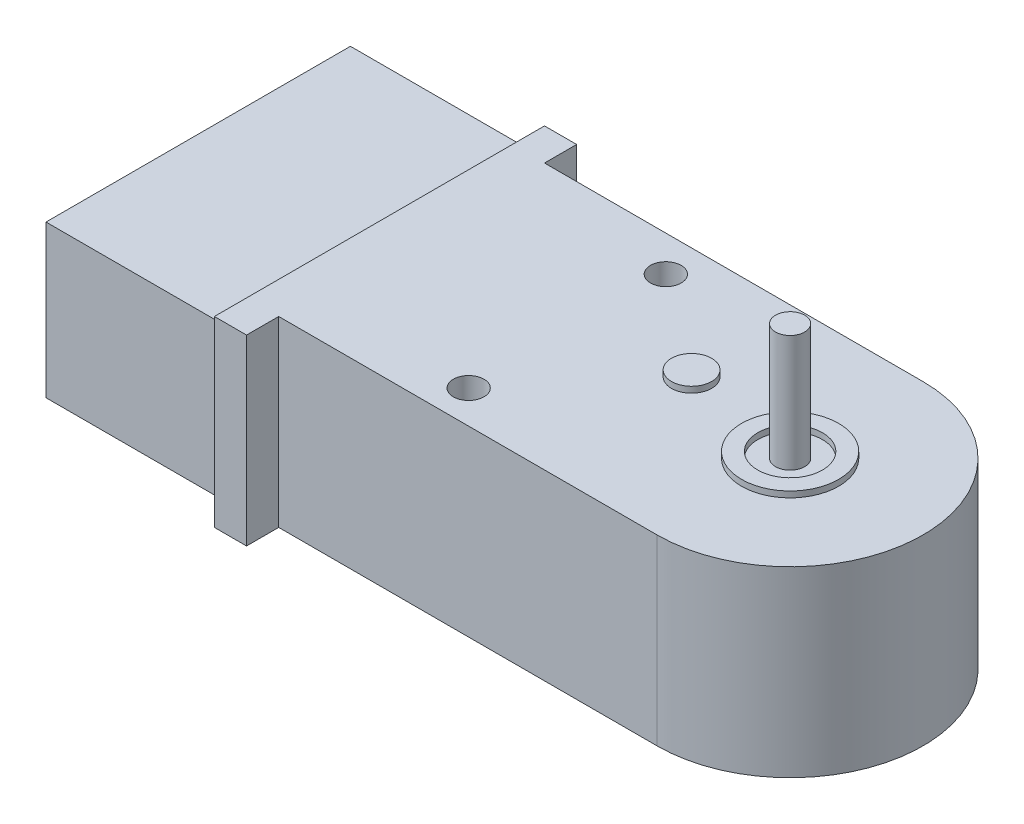
SolidWorks part; units mm, degrees
ref_plane "Front Plane" through (0, 0, 0) normal (0, 0, 1) x (1, 0, 0)
ref_plane "Top Plane" through (0, 0, 0) normal (0, 1, 0) x (1, 0, 0)
ref_plane "Right Plane" through (0, 0, 0) normal (1, 0, 0) x (0, 0, -1)
sketch "Sketch1" plane through (0, 0, 0) normal (0, 1, 0) x (1, 0, 0)
  line L0 (-30.84, 0) -> (0, 0) construction
  line L1 (0, 9.98) -> (-28.425, 9.98)
  line L2 (-28.425, 9.98) -> (-28.425, 12.395)
  line L3 (-28.425, 12.395) -> (-30.84, 12.395)
  line L4 (-30.84, 12.395) -> (-30.84, -12.395)
  line L5 (-30.84, -12.395) -> (-28.425, -12.395)
  line L6 (-28.425, -12.395) -> (-28.425, -9.98)
  line L7 (-28.425, -9.98) -> (0, -9.98)
  arc A0 (0, -9.98) -> (0, 9.98) centre (0, 0) ccw
  dimension "D1" = 19.96
  dimension "D2" = 30.84
  dimension "D3" = 24.79
extrude "Gear Box" add sketch "Sketch1" along normal blind 6.86 and the other way blind 6.86
sketch "Sketch2" plane through (0, 0, 0) normal (0, 1, 0) x (1, 0, 0)
  line L0 (0, 0) -> (-44.45, 0) construction
  line L1 (-30.84, 11.43) -> (-44.45, 11.43)
  line L2 (-30.84, 11.43) -> (-30.84, -11.43)
  line L3 (-30.84, -11.43) -> (-44.45, -11.43)
  line L4 (-44.45, 11.43) -> (-44.45, -11.43)
  line L5 (-30.84, 12.395) -> (-30.84, -12.395) construction
  dimension "D1" = 22.86
  dimension "D2" = 13.61
extrude "Motor" add sketch "Sketch2" along normal blind 5.715 and the other way blind 5.715
sketch "Sketch3" plane through (0, 6.86, 0) normal (0, 1, 0) x (1, 0, 0)
  line L0 (-30.84, 12.395) -> (-30.84, -12.395) construction
  line L1 (-28.425, -9.98) -> (0, -9.98) construction
  circle A0 centre (-9, 1.6) radius 1.51
  circle A1 centre (0, 0) radius 3.645
  circle A2 centre (0, 0) radius 2.43
  dimension "D1" = 3.02
  dimension "D4" = 7.29
  dimension "D5" = 4.86
  dimension "D2" = 21.84
  dimension "D3" = 11.58
extrude "Spacer" add sketch "Sketch3" along normal blind 0.45
sketch "Sketch5" plane through (0, -6.86, 0) normal (0, -1, 0) x (1, 0, 0)
  circle A0 centre (0, 0) radius 3.645
  circle A1 centre (0, 0) radius 2.43
  circle A2 centre (0, 0) radius 3.645 construction
  circle A3 centre (0, 0) radius 2.43 construction
extrude "Spacer(back)" add sketch "Sketch5" along normal blind 0.45
sketch "Sketch4" plane through (0, 6.86, 0) normal (0, 1, 0) x (1, 0, 0)
  circle A0 centre (0, 0) radius 1.095
  dimension "D1" = 2.19
extrude "Output Shaft" add sketch "Sketch4" along normal blind 8.76
sketch "Sketch7" plane through (0, 6.86, 0) normal (0, 1, 0) x (1, 0, 0)
  line L0 (-16.64, -7.5) -> (-16.64, 7.5)
  line L1 (-28.425, -9.98) -> (0, -9.98) construction
  line L2 (-30.84, 12.395) -> (-30.84, -12.395) construction
  circle A0 centre (-16.64, 7.3052) radius 1.15
  circle A1 centre (-16.64, -7.5) radius 1.15
  dimension "D3" = 2.3
  dimension "D4" = 2.3
  dimension "D1" = 15
  dimension "D2" = 2.48
  dimension "D5" = 14.2
extrude "Cut-Extrude1" cut sketch "Sketch7" against normal blind 5 contours A1 | A0 region at (-17.4302, 6.86, -8.0954) region at (-15.8498, 6.86, 6.7098)
